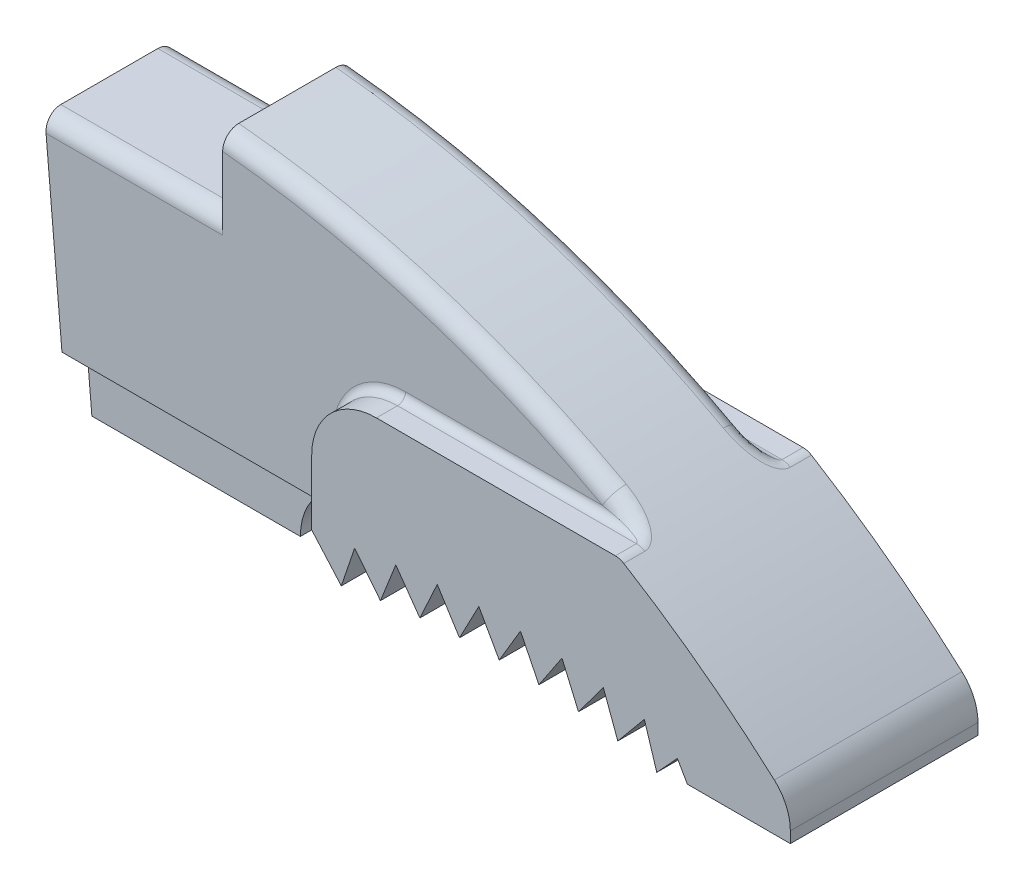
SolidWorks part; units mm, degrees
note: '?' marks a value the reader was unsure of.
ref_plane "Front Plane" through (0, 0, 0) normal (0, 0, 1) x (1, 0, 0)
ref_plane "Top Plane" through (0, 0, 0) normal (0, 1, 0) x (1, 0, 0)
ref_plane "Right Plane" through (0, 0, 0) normal (1, 0, 0) x (0, 0, -1)
sketch "Sketch1" plane through (0, 0, 0) normal (0, 0, 1) x (1, 0, 0)
  line L0 (0, 0) -> (0, 50.8039) construction
  line L1 (0, 0) -> (47.4869, 47.4869) construction
  line L2 (0, 0) -> (-4.2741, 48.8536) construction
  line L3 (-24.9861, 25.7175) -> (66.7901, 25.7175) construction
  line L4 (-3.459, 39.5365) -> (-2.25, 25.7175)
  line L5 (-2.25, 25.7175) -> (5.8796, 25.7175)
  line L6 (5.8796, 25.7175) -> (5.8796, 26.3525)
  line L7 (8.4196, 28.8925) -> (27.2088, 28.8925)
  circle A0 centre (0, 0) radius 39.6875 construction
  arc A1 (27.2088, 28.8925) -> (-3.459, 39.5365) centre (0, 0) ccw
  arc A2 (8.4196, 28.8925) -> (5.8796, 26.3525) centre (8.4196, 26.3525) ccw
  point P16 (5.8796, 28.8925)
  dimension "D1" = 79.375
  dimension "D4" = 13.97
  dimension "D8" = 2.54
  dimension "D2" = 45
  dimension "D3" = 5
  dimension "D5" = 5.8796
  dimension "D6" = 3.175
  dimension "D7" = 21.3292
extrude "Extrude1" add sketch "Sketch1" along normal mid plane 3.175
sketch "Sketch2" plane through (0, 0, 0) normal (0, 0, 1) x (1, 0, 0)
  line L0 (8.4196, 28.8925) -> (-2.5278, 28.8925)
  line L4 (-3.459, 39.5365) -> (-2.25, 25.7175)
  line L5 (-2.25, 25.7175) -> (5.8796, 25.7175)
  line L6 (5.8796, 25.7175) -> (5.8796, 26.3525)
  line L7 (8.4196, 28.8925) -> (27.2088, 28.8925)
  line L8 (-3.459, 39.5365) -> (-2.5278, 28.8925)
  line L11 (8.4196, 28.8925) -> (27.2088, 28.8925)
  arc A2 (27.2088, 28.8925) -> (-3.459, 39.5365) centre (0, 0) ccw
  arc A3 (8.4196, 28.8925) -> (5.8796, 26.3525) centre (8.4196, 26.3525) ccw
  arc A4 (27.2088, 28.8925) -> (-3.459, 39.5365) centre (0, 0) ccw
  dimension "D1" = 0
extrude "Extrude2" add sketch "Sketch2" along normal mid plane 5.08
sketch "Sketch3" plane through (0, 0, 0) normal (0, 0, 1) x (1, 0, 0)
  line L2 (27.2088, 28.8925) -> (8.4196, 28.8925)
  line L4 (20.5175, 33.9725) -> (8.4196, 33.9725)
  line L5 (8.4196, 28.8925) -> (8.4196, 33.9725)
  arc A0 (27.2088, 28.8925) -> (-3.459, 39.5365) centre (0, 0) ccw construction
  arc A1 (27.2088, 28.8925) -> (20.5175, 33.9725) centre (0, 0) ccw
  dimension "D1" = 5.08
extrude "Extrude3" add sketch "Sketch3" along normal mid plane 7.366
sketch "Sketch7" plane through (0, 0, 3.683) normal (0, 0, 1) x (1, 0, 0)
  line L0 (8.4196, 28.8925) -> (27.2088, 28.8925) construction
  line L1 (8.4196, 28.8925) -> (22.4336, 28.8925)
  arc A0 (8.4196, 28.8925) -> (22.4336, 28.8925) centre (15.4266, -1.6318) cw
  dimension "D1" = 31.3182
  dimension "D2" = 4.7752
extrude "Cut-Extrude1" cut sketch "Sketch7" against normal through all
sketch "Sketch4" plane through (0, 0, 0) normal (0, 0, 1) x (1, 0, 0)
  line L0 (8.4196, 28.8925) -> (9.5815, 27.5708)
  line L1 (9.5815, 27.5708) -> (10.1451, 29.2379)
  line L3 (9.5815, 27.5708) -> (9.2893, 29.0307) construction
  line L5 (8.4196, 33.9725) -> (8.4196, 28.8925) construction
  arc A1 (22.4336, 28.8925) -> (8.4196, 28.8925) centre (15.4266, -1.6318) ccw construction
  arc A2 (10.1451, 29.2379) -> (8.4196, 28.8925) centre (15.4266, -1.6318) ccw
  dimension "D1" = 30
  dimension "D2" = 30
  dimension "D4" = 1.7598
extrude "Extrude4" add sketch "Sketch4" along normal up to surface and the other way up to surface up to face at (17.4268, 31.1188, 3.683) other way up to face at (17.4268, 31.1188, -3.683)
ref_axis "Axis1" through (15.4266, -1.6318, 3.683) along (0, 0, -1)?
pattern_circular "CirPattern1" count 9 every 3 about axis through (15.4266, -1.6318, 0) along (0, 0, 1) of "Extrude4"
sketch "Sketch10" plane through (0, 0, 2.54) normal (0, 0, 1) x (1, 0, 0)
  line L1 (-7.2341, 44.5224) -> (3.7813, 44.5224)
  line L2 (-7.2341, 44.5224) -> (-7.2341, 36.6535)
  line L3 (-7.2341, 36.6535) -> (3.7813, 36.6535)
  line L4 (3.7813, 44.5224) -> (3.7813, 36.6535)
extrude "Cut-Extrude4" cut sketch "Sketch10" against normal through all
fillet "Fillet5" radius 2.54 2 edges at (8.4196, 33.9725, -3.1115) (8.4196, 33.9725, 3.1115)
fillet "Fillet4" radius 0.3175 6 edges at (15.7385, 33.9725, 2.54) (8.4196, 30.1625, 2.54) (8.4196, 30.1625, -2.54) (15.7385, 33.9725, -2.54) (9.1635, 33.2286, -2.54) (9.1635, 33.2286, 2.54)
fillet "Fillet6" radius 0.635 10 edges at (20.5175, 33.9725, 3.2702) (20.4507, 34.0128, 2.7028) (12.1648, 37.7772, 2.54) (20.5175, 33.9725, -3.2702) (20.4783, 33.9961, -2.7373) (2.9459, 28.8925, -1.5875) (2.9459, 28.8925, 1.5875) (12.1648, 37.7772, -2.54) (0.2873, 36.6535, -2.54) (0.2873, 36.6535, 2.54)
sketch "Sketch5" plane through (0, 28.8925, 0) normal (0, -1, 0) x (1, 0, 0)
  line L4 (22.4336, 3.683) -> (22.4336, -3.683)
  line L5 (22.4336, -3.683) -> (27.2088, -3.683)
  line L6 (27.2088, -3.683) -> (27.2088, 3.683)
  line L7 (27.2088, 3.683) -> (22.4336, 3.683)
  line L8 (22.4336, 3.683) -> (22.4336, -3.683)
  line L9 (22.4336, -3.683) -> (27.2088, -3.683)
  line L10 (27.2088, -3.683) -> (27.2088, 3.683)
  line L11 (27.2088, 3.683) -> (22.4336, 3.683)
  dimension "D1" = 0
extrude "Extrude5" add sketch "Sketch5" along normal blind 1.27
chamfer "Chamfer1" distance 1.27 angle 30 1 edges at (22.4336, 27.6225, 0)
fillet "Fillet7" radius 1.905 1 edges at (27.2088, 28.8925, 0)
sketch "Sketch9" plane through (5.8796, 0, 0) normal (1, 0, 0) x (0, 0, -1)
  line L4 (1.5875, 25.7175) -> (1.5875, 26.3525)
  line L5 (1.5875, 26.3525) -> (-1.5875, 26.3525)
  line L6 (-1.5875, 26.3525) -> (-1.5875, 25.7175)
  line L7 (-1.5875, 25.7175) -> (1.5875, 25.7175)
  line L8 (1.5875, 25.7175) -> (1.5875, 26.3525)
  line L9 (1.5875, 26.3525) -> (-1.5875, 26.3525)
  line L10 (-1.5875, 26.3525) -> (-1.5875, 25.7175)
  line L11 (-1.5875, 25.7175) -> (1.5875, 25.7175)
  dimension "D1" = 0
extrude "Cut-Extrude3" cut sketch "Sketch9" against normal through all
sketch "Sketch11" [suppressed] plane through (0, 0, -2.54) normal (0, 0, -1) x (-1, 0, 0)
  circle A0 centre (-2.54, 33.02) radius 1.8079
  dimension "D1" = 2.54
  dimension "D2" = 33.02
extrude "Cut-Extrude5" [suppressed] cut sketch "Sketch11" against normal blind 8.636
